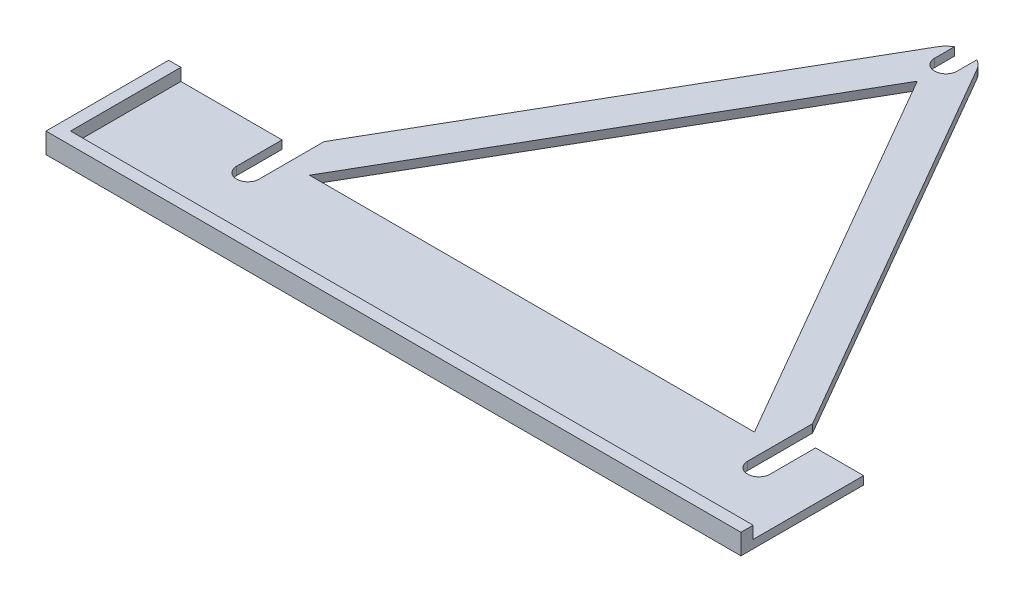
SolidWorks part; units mm, degrees
ref_plane "Front Plane" through (0, 0, 0) normal (0, 0, 1) x (1, 0, 0)
ref_plane "Top Plane" through (0, 0, 0) normal (0, 1, 0) x (1, 0, 0)
ref_plane "Right Plane" through (0, 0, 0) normal (1, 0, 0) x (0, 0, -1)
sketch "Sketch1" plane through (0, 0, 0) normal (0, 1, 0) x (1, 0, 0)
  line L0 (-62.5, -54.1266) -> (0, 54.1266) construction
  line L1 (0, 54.1266) -> (62.5, -54.1266) construction
  line L2 (62.5, -54.1266) -> (-62.5, -54.1266) construction
  line L6 (62.5, -43) -> (4.818, 56.9082)
  line L11 (-93, -73) -> (77, -73)
  line L17 (0, 54.1266) -> (0, 70) construction
  line L18 (0, -54.1266) -> (0, -70) construction
  line L19 (-93, -73) -> (77, -73)
  line L38 (-62.5, -43) -> (-93, -43)
  line L39 (62.5, -43) -> (77, -43)
  line L40 (-93, -43) -> (-93, -73)
  line L41 (77, -70) -> (-90, -70)
  line L42 (-90, -43) -> (-90, -70)
  line L43 (-54.4171, -47.1266) -> (0, 47.1266)
  line L44 (77, -43) -> (77, -73)
  line L45 (-4.818, 56.9082) -> (-62.5, -43)
  line L46 (0, 47.1266) -> (54.4171, -47.1266)
  line L47 (54.4171, -47.1266) -> (-54.4171, -47.1266)
  line L49 (-90, -70) -> (90, -70) construction
  line L50 (-90, -70) -> (-90, 70) construction
  line L51 (-90, 70) -> (90, 70) construction
  line L52 (90, -70) -> (90, 70) construction
  line L53 (-90, -70) -> (90, 70) construction
  line L54 (-90, 70) -> (90, -70) construction
  circle A0 centre (0, -18.0422) radius 36.0844 construction
  arc A1 (4.818, 56.9082) -> (-4.818, 56.9082) centre (0, 54.1266) ccw
  circle A4 centre (0, 54.1266) radius 2.75
  circle A5 centre (62.5, -54.1266) radius 2.75
  circle A6 centre (-62.5, -54.1266) radius 2.75
  point P10 (0, 0)
  point P11 (0, 0)
  point P14 (0, 0)
  point P30 (-62.5, -36.7695)
  point P31 (0, 70)
  point P32 (0, 0)
  point P33 (0, 0)
  point P34 (0, 0)
  point P35 (17.5488, -4.7187)
  point P36 (0, 0)
  point P37 (0, 0)
  point P39 (0, 0)
  point P41 (49.9432, -39.3776)
  point P42 (0, 0)
  point P43 (4.6768, 56.8267)
  point P44 (0, 0)
  point P45 (-2.7399, 55.6707)
  point P46 (-9.4054, 59.8245)
  dimension "D2" = 125
  dimension "D5" = 180
  dimension "D7" = 5.5
  dimension "D3" = 120
  dimension "D8" = 140
  dimension "D9" = 30
  dimension "D10" = 7
  dimension "D11" = 7
  dimension "D6" = 3
  dimension "D4" = 3
  dimension "D14" = 170
extrude "Boss-Extrude4" add sketch "Sketch1" along normal blind 2 contours L6 A1 A6 A5 A4 region at (69.75, 0, 45.1144)
extrude "Boss-Extrude7" add sketch "Sketch1<6>" along normal blind 5 contours L11 L40 region at (75.2737, 0, 71.5)
sketch "Sketch1<6>" plane through (0, 0, 0) normal (0, 1, 0) x (1, 0, 0) same geometry as "Sketch1"
sketch "Sketch2" plane through (0, 2, 0) normal (0, 1, 0) x (1, 0, 0)
  line L0 (-2.75, 54.1266) -> (-2.75, 58.9627)
  line L1 (-65.25, -54.1266) -> (-65.25, -43)
  line L2 (-62.5, -43) -> (-90, -43) construction
  line L3 (-59.75, -54.1266) -> (-59.75, -38.2369)
  line L4 (2.75, 54.1266) -> (2.75, 58.9627)
  line L5 (65.25, -54.1266) -> (65.25, -43)
  line L6 (62.5, -43) -> (77, -43) construction
  line L7 (59.75, -54.1266) -> (59.75, -38.2369)
  line L10 (-4.818, 56.9082) -> (-62.5, -43) construction
  line L11 (-59.75, -38.2369) -> (-62.5, -43)
  line L12 (-62.5, -43) -> (-65.25, -43)
  line L14 (62.5, -43) -> (4.818, 56.9082) construction
  line L15 (59.75, -38.2369) -> (62.5, -43)
  line L16 (62.5, -43) -> (65.25, -43)
  arc A0 (-65.25, -54.1266) -> (-59.75, -54.1266) centre (-62.5, -54.1266) ccw
  arc A1 (-2.75, 54.1266) -> (2.75, 54.1266) centre (0, 54.1266) ccw
  circle A2 centre (-62.5, -54.1266) radius 2.75 construction
  circle A6 centre (0, 54.1266) radius 2.75 construction
  arc A7 (4.818, 56.9082) -> (-4.818, 56.9082) centre (0, 54.1266) ccw construction
  arc A8 (59.75, -54.1266) -> (65.25, -54.1266) centre (62.5, -54.1266) ccw
  circle A9 centre (62.5, -54.1266) radius 2.75 construction
  arc A10 (-2.75, 58.9627) -> (2.75, 58.9627) centre (0, 54.1266) cw
extrude "Cut-Extrude1" cut sketch "Sketch2" against normal through all both and the other way through all
